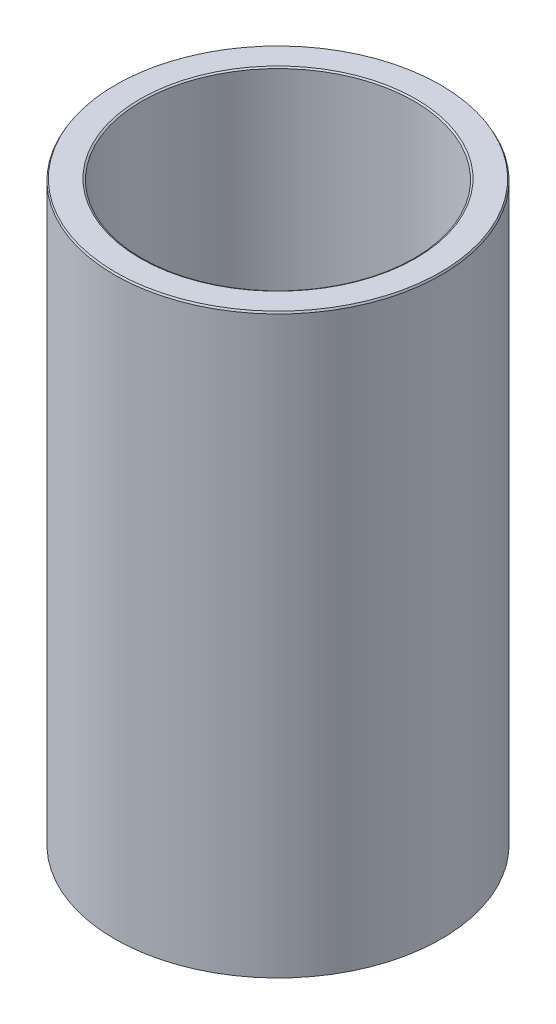
SolidWorks part; units mm, degrees
ref_plane "Front Plane" through (0, 0, 0) normal (0, 0, 1) x (1, 0, 0)
ref_plane "Top Plane" through (0, 0, 0) normal (0, 1, 0) x (1, 0, 0)
ref_plane "Right Plane" through (0, 0, 0) normal (1, 0, 0) x (0, 0, -1)
sketch "Sketch1" plane through (0, 0, 0) normal (0, 1, 0) x (1, 0, 0)
  circle A0 centre (0, 0) radius 45
  dimension "SLEEVE_OD" = 90
extrude "Boss-Extrude1" add sketch "Sketch1" along normal blind 159.1119
sketch "Sketch2" plane through (0, 0, 0) normal (0, 1, 0) x (1, 0, 0)
  circle A0 centre (0, 0) radius 37.4989
  dimension "BORE_D" = 74.9977
extrude "Cut-Extrude1" cut sketch "Sketch2" along normal through all
chamfer "Chamfer1" distance 0.4819 angle 30 4 edges at (0, 159.1119, 37.4989) (0, 0, 37.4989) (0, 0, 45) (0, 159.1119, 45) first distance on face at (0, 159.1119, 37.4989) first distance on face at (0, 0, 37.4989) first distance on face at (0, 159.1119, 45)
